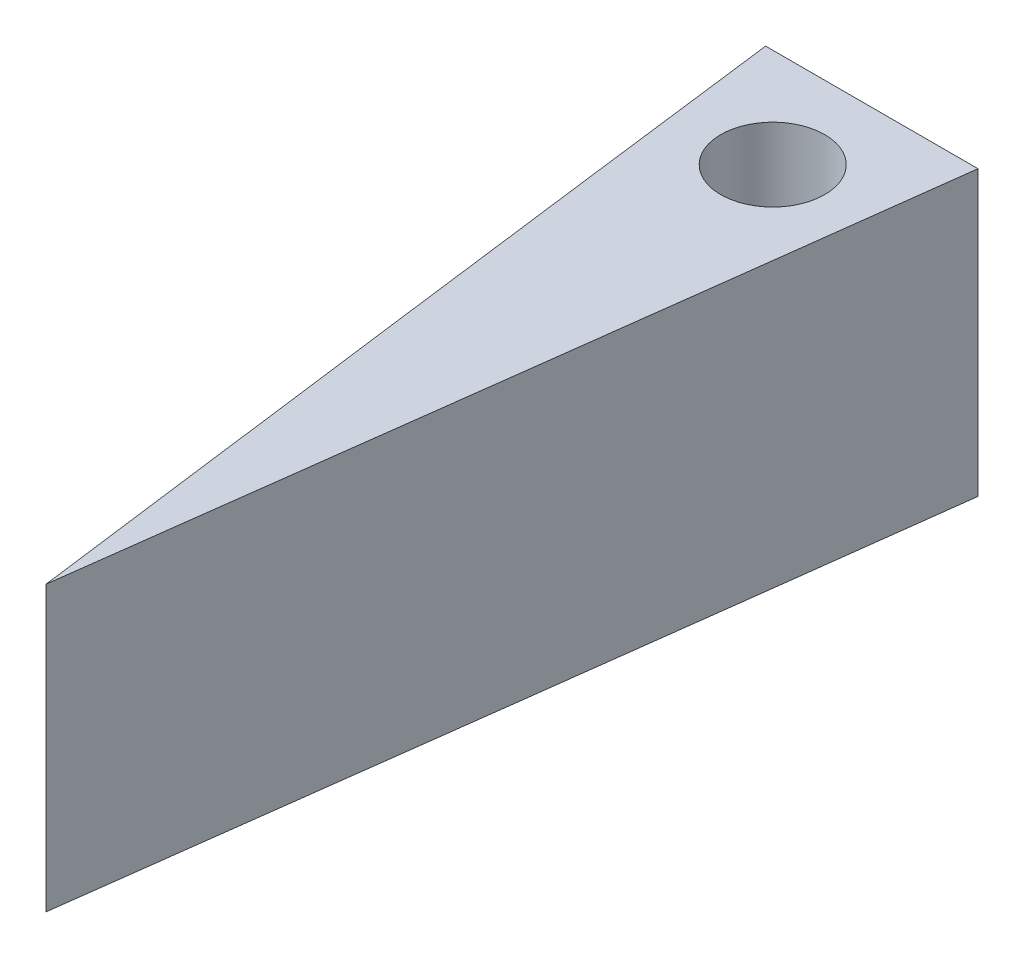
SolidWorks part; units mm, degrees
ref_plane "Front Plane" through (0, 0, 0) normal (0, 0, 1) x (1, 0, 0)
ref_plane "Top Plane" through (0, 0, 0) normal (0, 1, 0) x (1, 0, 0)
ref_plane "Right Plane" through (0, 0, 0) normal (1, 0, 0) x (0, 0, -1)
sketch "Sketch1" plane through (0, 0, 0) normal (0, 1, 0) x (1, 0, 0)
  line L0 (1.1081, 1.7265) -> (-45.0799, 1.7265) construction
  line L1 (-45.0799, 1.7265) -> (-45.0799, -11.2275) construction
  line L2 (-45.0799, -11.2275) -> (43.7517, -11.2275) construction
  line L3 (1.1081, 103.3269) -> (1.1081, -99.8738) construction
  line L4 (-45.0799, -11.2275) -> (-45.0799, -20.7525) construction
  line L5 (-28.2049, 1.7265) -> (-28.2049, -3.6075) construction
  line L6 (-9.9553, -3.6075) -> (-6.7697, -3.6075)
  line L7 (-28.2049, -3.6075) -> (-9.9553, -3.6075) construction
  line L8 (-6.7697, -3.6075) -> (1.1081, -3.6075) construction
  line L9 (8.9859, -3.6075) -> (12.1715, -3.6075)
  line L10 (12.1715, -3.6075) -> (18.1346, -3.6075) construction
  line L11 (12.1715, -3.6075) -> (18.1346, -3.6075) construction
  line L12 (18.1346, -3.6075) -> (29.3788, -3.6075) construction
  line L13 (1.1081, -3.6075) -> (8.9859, -3.6075) construction
  line L14 (-6.7697, -3.6075) -> (8.9859, -3.6075)
  circle A0 centre (1.1081, -11.3265) radius 1.9844 construction
  circle A1 centre (1.1081, -11.3265) radius 1.9844
  spline S0 degree 3 poles (1.1081, -99.8738) (4.5273, -73.5318) (7.9866, -47.1872) (10.6029, -20.7525) knots 0 0 0 0 0.38497 0.38497 0.38497 0.38497
  spline S3 degree 3 poles (1.1081, -99.8738) (-2.3112, -73.5318) (-5.7704, -47.1872) (-8.3867, -20.7525) knots 0 0 0 0 0.38497 0.38497 0.38497 0.38497
  spline S4 degree 3 poles (10.6029, -20.7525) (11.1, -15.7302) (11.6306, -10.016) (12.114, -4.2968) (12.1715, -3.6075) knots 0.38497 0.38497 0.38497 0.38497 0.458109 0.468132 0.468132 0.468132 0.468132
  spline S5 degree 3 poles (-8.3867, -20.7525) (-8.8838, -15.7302) (-9.4144, -10.016) (-9.8978, -4.2968) (-9.9553, -3.6075) knots 0.38497 0.38497 0.38497 0.38497 0.458109 0.468132 0.468132 0.468132 0.468132
  spline S8 degree 3 poles (12.1715, -3.6075) (12.8364, 4.367) (14.1908, 23.6726) (14.0058, 48.0803) (13.0188, 67.5796) (11.3266, 78.9472) (9.5869, 86.9693) (8.1237, 93.6397) (6.4505, 97.563) (4.8164, 101.3994) (2.3437, 102.5279) (1.1081, 103.3269) knots 0.468132 0.468132 0.468132 0.468132 0.584075 0.748482 0.821537 0.866809 0.914778 0.94069 0.965303 0.976863 1 1 1 1 construction
  spline S9 degree 3 poles (1.1081, 99.6196) (1.2739, 99.518) (1.6209, 99.2976) (2.0134, 99.0137) (2.3095, 98.7539) (2.4667, 98.5788) (2.6076, 98.3713) (2.8163, 97.9774) (3.0534, 97.4394) (3.4327, 96.5453) (3.8774, 95.496) (4.541, 93.8448) (5.2023, 91.9048) (5.8236, 89.3366) (6.4213, 86.5662) (7.0145, 83.8293) (7.767, 80.1951) (8.6007, 75.6781) (9.6391, 68.4081) (10.3034, 59.2354) (10.6788, 47.9926) (10.8555, 36.7918) (10.7415, 25.5951) (10.3009, 14.4244) (9.6564, 4.6878) (9.1767, -1.3266) (8.9859, -3.6075) knots 0.118744 0.118744 0.118744 0.118744 0.122149 0.125554 0.12896 0.132365 0.13577 0.139175 0.142581 0.145986 0.152796 0.159607 0.173228 0.186849 0.20047 0.214091 0.227711 0.254953 0.282195 0.336679 0.391163 0.445646 0.50013 0.554614 0.609098 0.642376 0.642376 0.642376 0.642376 construction
  spline S10 degree 3 poles (-7.1984, 1.7265) (-7.237, 2.2289) (-7.5577, 6.4638) (-8.0847, 14.4244) (-8.5253, 25.5951) (-8.6393, 36.7918) (-8.4626, 47.9926) (-8.0872, 59.2354) (-7.4229, 68.4081) (-6.3845, 75.6781) (-5.5508, 80.1951) (-4.7983, 83.8293) (-4.2051, 86.5662) (-3.6074, 89.3366) (-2.9861, 91.9048) (-2.3248, 93.8448) (-1.6612, 95.496) (-1.2165, 96.5453) (-0.8372, 97.4394) (-0.6001, 97.9774) (-0.3914, 98.3713) (-0.2505, 98.5788) (-0.0933, 98.7539) (0.2028, 99.0137) (0.5953, 99.2976) (0.9423, 99.518) (1.1081, 99.6196) knots 0.492798 0.492798 0.492798 0.492798 0.50013 0.554614 0.609098 0.663581 0.718065 0.772549 0.827033 0.854275 0.881516 0.895137 0.908758 0.922379 0.936 0.949621 0.956432 0.963242 0.966647 0.970053 0.973458 0.976863 0.980268 0.983674 0.987079 0.990484 0.990484 0.990484 0.990484 construction
  spline S11 degree 3 poles (-10.3826, 1.7265) (-10.8572, 7.9268) (-11.9611, 25.4575) (-11.7896, 48.0803) (-10.8026, 67.5796) (-9.1104, 78.9472) (-7.3707, 86.9693) (-5.9075, 93.6397) (-4.2343, 97.563) (-2.6002, 101.3994) (-0.1276, 102.5279) (1.1081, 103.3269) knots 0.493976 0.493976 0.493976 0.493976 0.584075 0.748482 0.821537 0.866809 0.914778 0.94069 0.965303 0.976863 1 1 1 1 construction
  spline S12 degree 3 poles (-9.9553, -3.6075) (-10.1035, -1.8299) (-10.2465, -0.0519) (-10.3826, 1.7265) knots 0.468132 0.468132 0.468132 0.468132 0.493976 0.493976 0.493976 0.493976 construction
  spline S13 degree 3 poles (-6.7697, -3.6075) (-6.9185, -1.8292) (-7.0618, -0.0511) (-7.1984, 1.7265) knots 0.466852 0.466852 0.466852 0.466852 0.492798 0.492798 0.492798 0.492798 construction
  dimension "D4" = 3.9688
  dimension "D1" = 12.954
  dimension "D2" = 9.525
  dimension "D3" = 5.334
extrude "Boss-Extrude1" add sketch "Sketch1" along normal blind 169.8727
sketch "Sketch2" plane through (0, 169.8727, 0) normal (0, 1, 0) x (1, 0, 0)
  line L1 (-9.9553, -3.6075) -> (25.8085, -3.6075)
  line L2 (-9.9553, -3.6075) -> (-9.9553, -26.3125)
  line L3 (-9.9553, -26.3125) -> (25.8085, -26.3125)
  line L4 (25.8085, -3.6075) -> (25.8085, -26.3125)
  circle A0 centre (1.1081, -11.3265) radius 1.9844 construction
  dimension "D1" = 14.986
extrude "Cut-Extrude1" cut sketch "Sketch2" against normal blind 23.0581
extrude "Cut-Extrude2" cut sketch "Sketch2<2>" along normal blind 23.0581 from surface starting at face at (-1.1046, 0, 29.7187)
sketch "Sketch2<2>" plane through (0, 169.8727, 0) normal (0, 1, 0) x (1, 0, 0) same geometry as "Sketch2"
fillet "Fillet1" radius 7.62 6 edges at (-7.8242, 11.5291, 26.3125) (10.0403, 11.5291, 26.3125) (12.1715, 84.9363, 3.6075) (-7.8242, 158.3436, 26.3125) (10.0403, 158.3436, 26.3125)
sketch "Sketch6" plane through (0, 0, 0) normal (0, -1, 0) x (1, 0, 0)
  line L0 (1.1081, 3.6075) -> (1.1081, 99.8738) construction
  line L1 (-1.6395, 3.6075) -> (3.8557, 3.6075) construction
  line L2 (-6.9254, 34.7606) -> (9.1416, 34.7606) construction
  circle A0 centre (1.1081, 71.9338) radius 2
  circle A1 centre (1.1081, 34.7606) radius 2
  dimension "D1" = 4
  dimension "D2" = 27.94
extrude "Cut-Extrude3" cut sketch "Sketch6" against normal through all both and the other way through all
sketch "Sketch7" plane through (0, 0, 0) normal (1, 0, 0) x (0, 0, -1)
  line L0 (-3.6075, 146.8145) -> (-3.6075, 23.0581) construction
  line L1 (-99.8738, 0) -> (-3.6075, 0)
  line L2 (-99.8738, 0) -> (-99.8738, 154.1951)
  line L3 (-99.8738, 154.1951) -> (-3.6075, 154.1951)
  line L4 (-3.6075, 0) -> (-3.6075, 154.1951)
  line L6 (-99.8738, 169.8727) -> (-3.6075, 169.8727)
  line L7 (-99.8738, 169.8727) -> (-99.8738, 165.1069)
  line L8 (-99.8738, 165.1069) -> (-3.6075, 165.1069)
  line L9 (-3.6075, 169.8727) -> (-3.6075, 165.1069)
  dimension "D2" = 10.9118
extrude "Cut-Extrude4" cut sketch "Sketch7" against normal through all both and the other way through all
sketch "Sketch8" plane through (0, 154.1951, 0) normal (0, -1, 0) x (1, 0, 0)
  line L1 (-35.7382, 68.1238) -> (19.5961, 68.1238)
  line L2 (-35.7382, 68.1238) -> (-35.7382, 26.3125)
  line L3 (-35.7382, 26.3125) -> (19.5961, 26.3125)
  line L4 (19.5961, 68.1238) -> (19.5961, 26.3125)
  dimension "D1" = 0
  dimension "D2" = 31.75
extrude "Cut-Extrude5" cut sketch "Sketch8" against normal through all both
